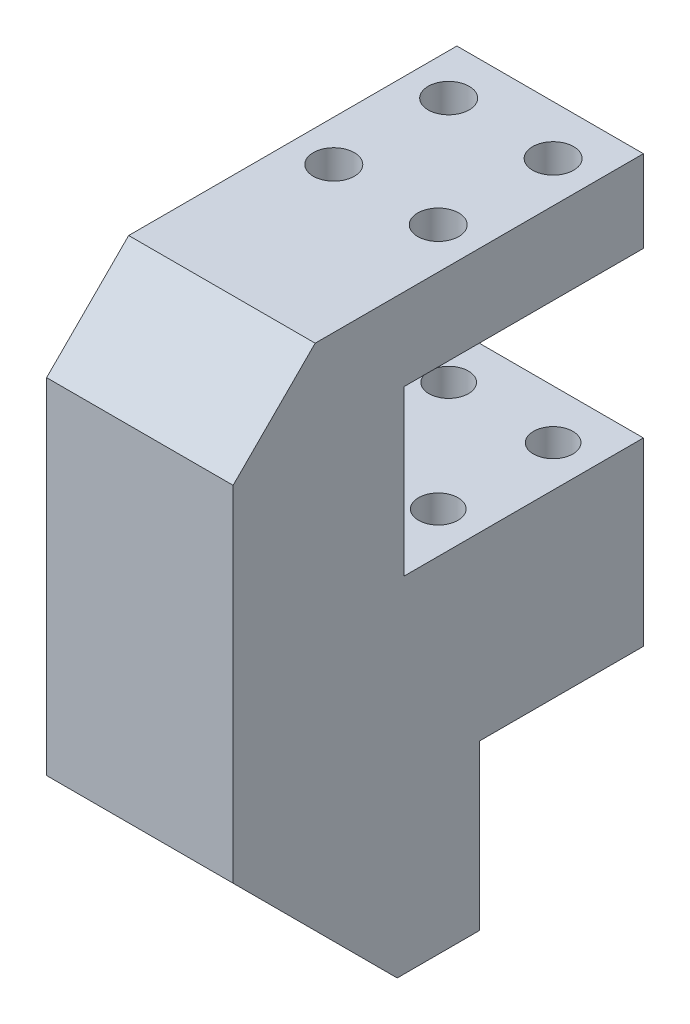
SolidWorks part; units mm, degrees
ref_plane "Front Plane" through (0, 0, 0) normal (0, 0, 1) x (1, 0, 0)
ref_plane "Top Plane" through (0, 0, 0) normal (0, 1, 0) x (1, 0, 0)
ref_plane "Right Plane" through (0, 0, 0) normal (1, 0, 0) x (0, 0, -1)
sketch "Sketch1" plane through (0, 0, 0) normal (0, 1, 0) x (1, 0, 0)
  line L1 (0, 0) -> (-12.73, 0)
  line L2 (0, 0) -> (0, 14)
  line L3 (0, 14) -> (-12.73, 14)
  line L4 (-12.73, 0) -> (-12.73, 14)
  line L5 (5, 20) -> (-17.73, 20)
  line L6 (5, 20) -> (5, -10)
  line L7 (5, -10) -> (-17.73, -10)
  line L8 (-17.73, 20) -> (-17.73, -10)
  circle A0 centre (-12.73, 14) radius 2.5
  circle A1 centre (0, 0) radius 2.5
  dimension "D3" = 5
  dimension "D1" = 14
  dimension "D2" = 12.73
  dimension "D4" = 5
  dimension "D5" = 5
  dimension "D6" = 20
  dimension "D7" = 10
sketch "Sketch2" plane through (0, 0, 0) normal (0, 1, 0) x (1, 0, 0)
  line L0 (5, 20) -> (-17.73, 20) construction
  line L1 (-17.73, 20) -> (-17.73, -10) construction
  line L2 (5, 20) -> (5, -10) construction
  line L3 (5, -10) -> (-17.73, -10) construction
  line L4 (5, 20) -> (-17.73, 20)
  line L5 (-17.73, 20) -> (-17.73, -10)
  line L6 (5, 20) -> (5, -10)
  line L7 (5, -10) -> (-17.73, -10)
extrude "Boss-Extrude1" add sketch "Sketch2" along normal blind 52
sketch "Sketch3" plane through (0, 0, 0) normal (0, -1, 0) x (1, 0, 0)
  line L0 (-17.73, -20) -> (-17.73, 10) construction
  line L1 (5, 10) -> (-17.73, 10)
  line L2 (5, 10) -> (5, 0)
  line L3 (5, 0) -> (-17.73, 0)
  line L4 (-17.73, 10) -> (-17.73, 0)
  dimension "D1" = 10
extrude "Boss-Extrude2" add sketch "Sketch3" along normal blind 20
sketch "Sketch4" plane through (0, 0, 10) normal (0, 0, 1) x (1, 0, 0)
  line L0 (-6.365, 0) -> (-6.365, -20) construction
  line L1 (5, -20) -> (-17.73, -20) construction
  line L2 (0, 0) -> (-6.365, 0) construction
  point P4 (-6.365, -10)
  point P6 (-6.365, -10)
  dimension "D1" = 10
  dimension "D2" = 10
hole_wizard "CBORE for M5 SHCS1" positions "Sketch5" profile "Sketch6" counterbore size "M5" standard "ANSI Metric" end condition through all
sketch "Sketch5" plane through (0, 0, 10) normal (0, 0, 1) x (1, 0, 0)
  point P3 (-6.365, -10)
sketch "Sketch6" plane through (-6.365, -10, 10) normal (1, 0, 0) x (0, -1, 0)
  line L0 (0, 0) -> (0, 30)
  line L1 (0, 30) -> (2.75, 30)
  line L3 (2.75, 30) -> (2.75, 5)
  line L4 (2.75, 5) -> (5, 5)
  line L5 (5, 5) -> (5, 0)
  line L7 (5, 0) -> (0, 0)
  line L11 (0, -6.35) -> (0, 107.95) construction
  dimension "Thru Hole Dia." = 5.5
  dimension "Thru Hole Depth" = 30
  dimension "C'Bore Dia." = 10
  dimension "C'Bore Depth" = 5
sketch "Sketch7" plane through (0, 0, 10) normal (0, 0, 1) x (1, 0, 0)
  line L4 (-17.73, 52) -> (-17.73, -20)
  line L5 (-17.73, -20) -> (5, -20)
  line L6 (5, -20) -> (5, 52)
  line L7 (5, 52) -> (-17.73, 52)
  line L8 (-17.73, 52) -> (-17.73, -20)
  line L9 (-17.73, -20) -> (5, -20)
  line L10 (5, -20) -> (5, 52)
  line L11 (5, 52) -> (-17.73, 52)
  circle A4 centre (-6.365, -10) radius 5 construction
  circle A5 centre (-6.365, -10) radius 5
  dimension "D1" = 0
extrude "Boss-Extrude3" add sketch "Sketch7" along normal blind 20
sketch "Sketch8" plane through (5, 0, 0) normal (1, 0, 0) x (0, 0, -1)
  line L0 (20, 52) -> (20, 0) construction
  line L1 (20, 42) -> (-9.2, 42)
  line L2 (20, 42) -> (20, 22)
  line L3 (20, 22) -> (-9.2, 22)
  line L4 (-9.2, 42) -> (-9.2, 22)
  line L5 (-30, 52) -> (20, 52) construction
  dimension "D1" = 20
  dimension "D2" = 10
  dimension "D3" = 9.2
extrude "Cut-Extrude1" cut sketch "Sketch8" against normal through all
sketch "Sketch9" plane through (0, 52, 0) normal (0, 1, 0) x (1, 0, 0)
  circle A1 centre (-12.73, 0) radius 2.5
  circle A2 centre (0, 14) radius 2.5
  circle A3 centre (-12.73, 14) radius 2.5
  circle A4 centre (0, 0) radius 2.5
  dimension "D1" = 5
extrude "Cut-Extrude2" cut sketch "Sketch9" against normal up to next
sketch "Sketch10" plane through (0, 22, 0) normal (0, 1, 0) x (1, 0, 0)
  circle A0 centre (0, 0) radius 2.4
  circle A1 centre (-12.73, 0) radius 2.4
  circle A2 centre (-12.73, 14) radius 2.4
  circle A3 centre (0, 14) radius 2.4
  dimension "D1" = 4.8
extrude "Cut-Extrude3" cut sketch "Sketch10" against normal blind 20
sketch "Sketch11" plane through (5, 0, 0) normal (1, 0, 0) x (0, 0, -1)
  line L10 (20, 0) -> (20, 22)
  line L11 (20, 22) -> (-9.2, 22)
  line L12 (-9.2, 22) -> (-9.2, 42)
  line L13 (-9.2, 42) -> (20, 42)
  line L14 (20, 42) -> (20, 52)
  line L15 (20, 52) -> (-30, 52)
  line L16 (-30, 52) -> (-30, -20)
  line L17 (-30, -20) -> (0, -20)
  line L18 (0, -20) -> (0, 0)
  line L19 (0, 0) -> (20, 0)
  line L20 (20, 0) -> (20, 22)
  line L21 (20, 22) -> (-9.2, 22)
  line L22 (-9.2, 22) -> (-9.2, 42)
  line L23 (-9.2, 42) -> (20, 42)
  line L24 (20, 42) -> (20, 52)
  line L25 (20, 52) -> (-30, 52)
  line L26 (-30, 52) -> (-30, -20)
  line L27 (-30, -20) -> (0, -20)
  line L28 (0, -20) -> (0, 0)
  line L29 (0, 0) -> (20, 0)
  dimension "D1" = 0
sketch "Sketch12" plane through (0, 0, -20) normal (0, 0, -1) x (-1, 0, 0)
  line L0 (-5, 0) -> (17.73, 0) construction
  line L1 (17.73, 22) -> (37.73, 22)
  line L2 (17.73, 22) -> (17.73, 0)
  line L3 (17.73, 0) -> (37.73, 0)
  line L4 (37.73, 22) -> (37.73, 0)
  dimension "D1" = 20
extrude "Boss-Extrude5" add sketch "Sketch12" against normal blind 20
sketch "Sketch13" plane through (0, 22, 0) normal (0, 1, 0) x (1, 0, 0)
  line L0 (-17.73, 0) -> (-37.73, 20) construction
hole_wizard "CBORE for M5 SHCS2" positions "Sketch14" profile "Sketch15" counterbore size "M5" standard "ANSI Metric" end condition through all
sketch "Sketch14" plane through (0, 22, 0) normal (0, 1, 0) x (1, 0, 0)
  line L0 (-17.73, 0) -> (-37.73, 20) construction
  point P0 (-27.73, 10)
sketch "Sketch15" plane through (-27.73, 22, -10) normal (1, 0, 0) x (0, 0, 1)
  line L0 (0, 0) -> (0, 42)
  line L1 (0, 42) -> (2.75, 42)
  line L3 (2.75, 42) -> (2.75, 16)
  line L4 (2.75, 16) -> (5, 16)
  line L5 (5, 16) -> (5, 0)
  line L7 (5, 0) -> (0, 0)
  line L11 (0, -6.35) -> (0, 107.95) construction
  dimension "Thru Hole Dia." = 5.5
  dimension "Thru Hole Depth" = 42
  dimension "C'Bore Dia." = 10
  dimension "C'Bore Depth" = 16
chamfer "Chamfer1" distance 20 angle 45 2 edges at (-6.365, -20, 30) (-37.73, 22, -10)
chamfer "Chamfer3" distance 10 angle 45 1 edges at (-6.365, 52, 30)
